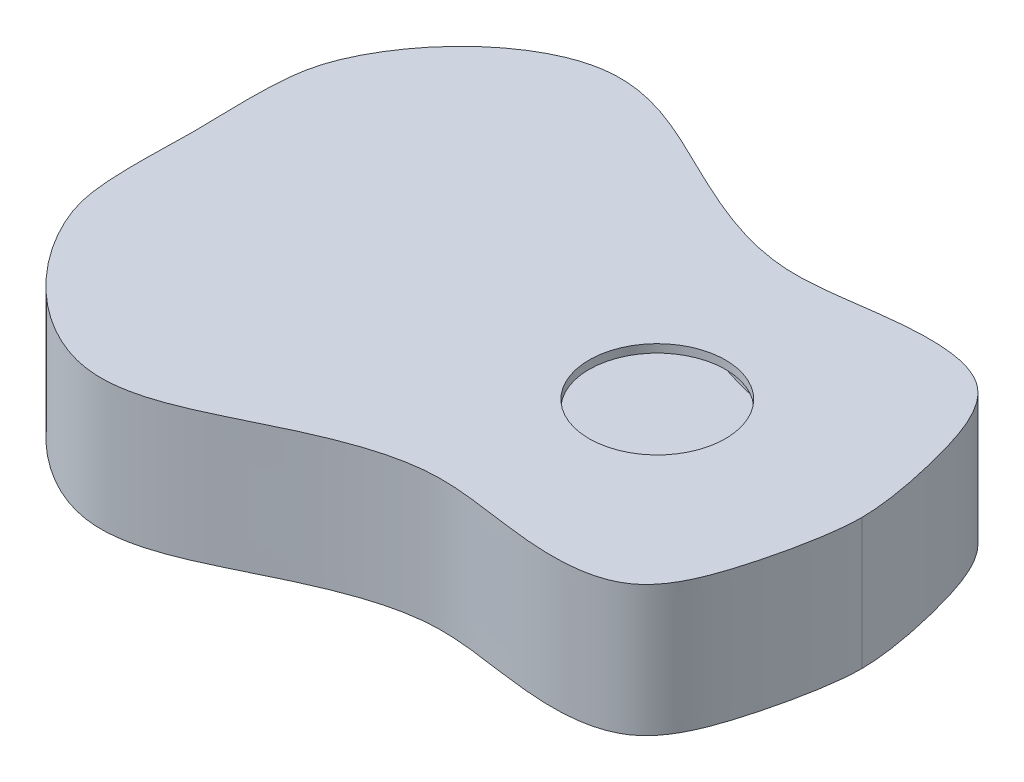
SolidWorks part; units mm, degrees
ref_plane "Front Plane" through (0, 0, 0) normal (0, 0, 1) x (1, 0, 0)
ref_plane "Top Plane" through (0, 0, 0) normal (0, 1, 0) x (1, 0, 0)
ref_plane "Right Plane" through (0, 0, 0) normal (1, 0, 0) x (0, 0, -1)
sketch "Sketch1" plane through (0, 0, 0) normal (0, 1, 0) x (1, 0, 0)
  line L0 (-114.6518, 0) -> (130.3482, 0) construction
  line L1 (130.3482, 0) -> (130.3482, 100) construction
  line L2 (-114.6518, 0) -> (-114.6518, 100) construction
  line L3 (-114.6518, 10.8456) -> (-114.6518, -10.8456) construction
  line L4 (130.3482, -7.0424) -> (130.3482, 7.0424) construction
  spline S0 degree 3 poles (-114.6518, 0) (-114.6518, 10.2832) (-116.1837, 33.4612) (-105.0227, 68.0328) (-63.704, 107.9273) (-9.8232, 79.9171) (31.9079, 61.1656) (71.697, 69.1756) (112.0558, 70.6856) (125.6615, 34.5931) (130.3482, 8.9918) (130.3482, 0) knots 0 0 0 0 0.091095 0.122896 0.318011 0.456437 0.60337 0.696406 0.808486 0.895846 1 1 1 1
  spline S1 degree 3 poles (-114.6518, 0) (-114.6518, -10.2832) (-116.1837, -33.4612) (-105.0227, -68.0328) (-63.704, -107.9273) (-9.8232, -79.9171) (31.9079, -61.1656) (71.697, -69.1756) (112.0558, -70.6856) (125.6615, -34.5931) (130.3482, -8.9918) (130.3482, 0) knots 0 0 0 0 0.091095 0.122896 0.318011 0.456437 0.60337 0.696406 0.808486 0.895846 1 1 1 1
  point P3 (-112.9018, 43)
  point P6 (-57.4018, 95)
  point P7 (-10.9018, 81)
  point P8 (38.0982, 65)
  point P9 (70.5982, 68)
  point P10 (109.5982, 63)
  point P11 (124.0982, 36)
  dimension "D1" = 245
  dimension "D2" = 100
  dimension "D3" = 100
  dimension "D4" = 43
  dimension "D5" = 3.5
  dimension "D6" = 55.5
  dimension "D7" = 95
  dimension "D8" = 46.5
  dimension "D9" = 81
  dimension "D10" = 65
  dimension "D11" = 49
  dimension "D12" = 68
  dimension "D13" = 32.5
  dimension "D14" = 63
  dimension "D15" = 39
  dimension "D16" = 36
  dimension "D17" = 14.5
extrude "Boss-Extrude1" add sketch "Sketch1" along normal blind 45
shell "Shell1" thickness 3 removed face at (7.8482, 45, 0)
sketch "Sketch2" plane through (0, 45, 0) normal (0, 1, 0) x (1, 0, 0)
  spline S0 degree 3 poles (-1683.8019, -4746.7116) (52.4448, 480.1826) (-138.1425, 34.5565) (-105.0227, -68.0328) (-63.704, -107.9273) (-9.8232, -79.9171) (31.9079, -61.1656) (71.697, -69.1756) (112.0558, -70.6856) (166.5006, 73.7433) (86.7389, 298.7933) (-1390.3694, -4760.5412) knots -0.625669 -0.625669 -0.625669 -0.625669 0.091095 0.122896 0.318011 0.456437 0.60337 0.696406 0.808486 0.895846 1.911278 1.911278 1.911278 1.911278 only from (-114.6518, 0) to (130.3482, 0) construction
  spline S1 degree 3 poles (-1390.4018, 4760.652) (86.7379, -298.7963) (166.5009, -73.7442) (112.0558, 70.6856) (71.697, 69.1756) (31.9079, 61.1656) (-9.8232, 79.9171) (-63.704, 107.9273) (-105.0227, 68.0328) (-138.1425, -34.5566) (52.445, -480.1832) (-1683.8057, 4746.723) knots -0.911286 -0.911286 -0.911286 -0.911286 0.104154 0.191514 0.303594 0.39663 0.543563 0.681989 0.877104 0.908905 1.625669 1.625669 1.625669 1.625669 only from (130.3482, 0) to (-114.6518, 0) construction
  spline S2 degree 3 poles (-114.6518, 0) (-114.6518, -10.2832) (-116.1837, -33.4612) (-105.0227, -68.0328) (-63.704, -107.9273) (-9.8232, -79.9171) (31.9079, -61.1656) (71.697, -69.1756) (112.0558, -70.6856) (125.6615, -34.5931) (130.3482, -8.9918) (130.3482, 0) knots 0 0 0 0 0.091095 0.122896 0.318011 0.456437 0.60337 0.696406 0.808486 0.895846 1 1 1 1
  spline S3 degree 3 poles (130.3482, 0) (130.3482, 8.9918) (125.6615, 34.5931) (112.0558, 70.6856) (71.697, 69.1756) (31.9079, 61.1656) (-9.8232, 79.9171) (-63.704, 107.9273) (-105.0227, 68.0328) (-116.1837, 33.4612) (-114.6518, 10.2832) (-114.6518, 0) knots 0 0 0 0 0.104154 0.191514 0.303594 0.39663 0.543563 0.681989 0.877104 0.908905 1 1 1 1
extrude "Boss-Extrude2" add sketch "Sketch2" along normal blind 3
sketch "Sketch3" plane through (0, 48, 0) normal (0, 1, 0) x (1, 0, 0)
  line L0 (-114.6518, 0) -> (192.0525, 0) construction
  circle A0 centre (55.3482, 0) radius 25
  point P6 (60.8181, 0)
  dimension "D1" = 50
  dimension "D2" = 75
extrude "Cut-Extrude1" cut sketch "Sketch3" against normal blind 4
sketch "Sketch4" plane through (0, 48, 0) normal (0, 1, 0) x (1, 0, 0)
  line L0 (-114.6518, 0) -> (178.3637, 0) construction
  line L1 (14.6926, 29.4608) -> (14.6926, -29.4608)
  arc A0 (14.6926, -29.4608) -> (14.6926, 29.4608) centre (24.665, 0) cw
  point P6 (14.6926, 0)
